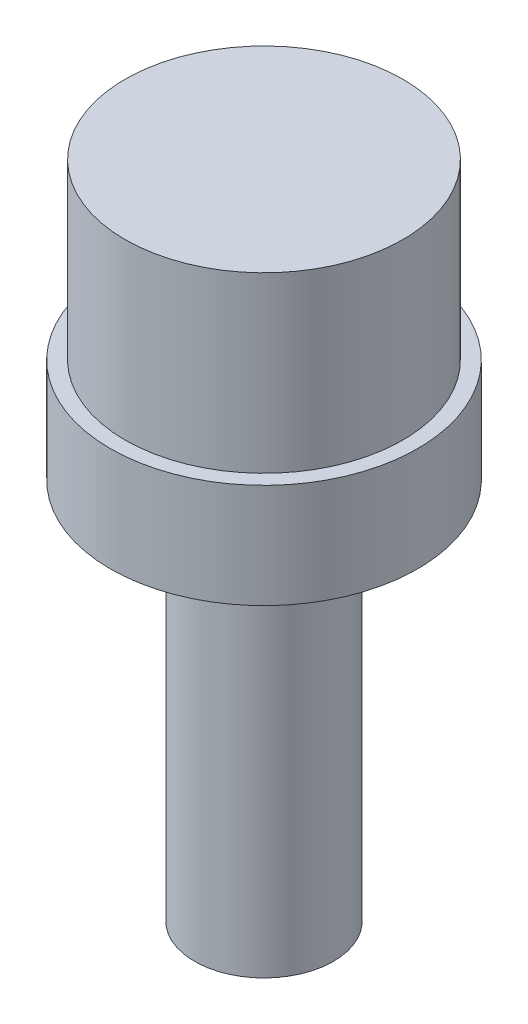
SolidWorks part; units mm, degrees
ref_plane "Front Plane" through (0, 0, 0) normal (0, 0, 1) x (1, 0, 0)
ref_plane "Top Plane" through (0, 0, 0) normal (0, 1, 0) x (1, 0, 0)
ref_plane "Right Plane" through (0, 0, 0) normal (1, 0, 0) x (0, 0, -1)
sketch "Sketch1" plane through (0, 0, 0) normal (0, 1, 0) x (1, 0, 0)
  line L0 (-1.3229, 1.5) -> (1.3229, 1.5)
  circle A0 centre (0, 0) radius 4
  circle A1 centre (0, 0) radius 4.425
  circle A2 centre (0, 0) radius 2
  dimension "D1" = 8
  dimension "D2" = 4
  dimension "D3" = 8.85
  dimension "D4" = 0.5
extrude "Boss-Extrude1" add sketch "Sketch1" along normal blind 3 contours L0 A2 | L0 A2 | A1 A2 | A0 A1 | A1 A0 region at (0, 0, -1.7023) region at (0, 0, 0.1324) region at (-3.8869, 0, 0) region at (-4.2998, 0, 0)
extrude "Boss-Extrude2" add sketch "Sketch1<3>" along normal offset from surface (8 mm away) 5 contours A0 A2 | L0 A2 | L0 A2 region at (0, 0, -1.7023) region at (0, 0, 0.1324) region at (-3.8869, 0, 0) up to face at (0, 3, 4.425) offset beyond the face yes
sketch "Sketch1<3>" plane through (0, 0, 0) normal (0, 1, 0) x (1, 0, 0) same geometry as "Sketch1"
extrude "Boss-Extrude3" add sketch "Sketch1<4>" against normal blind 11 contours L0 A2 region at (0, 0, 0.1324)
sketch "Sketch1<4>" plane through (0, 0, 0) normal (0, 1, 0) x (1, 0, 0) same geometry as "Sketch1"
